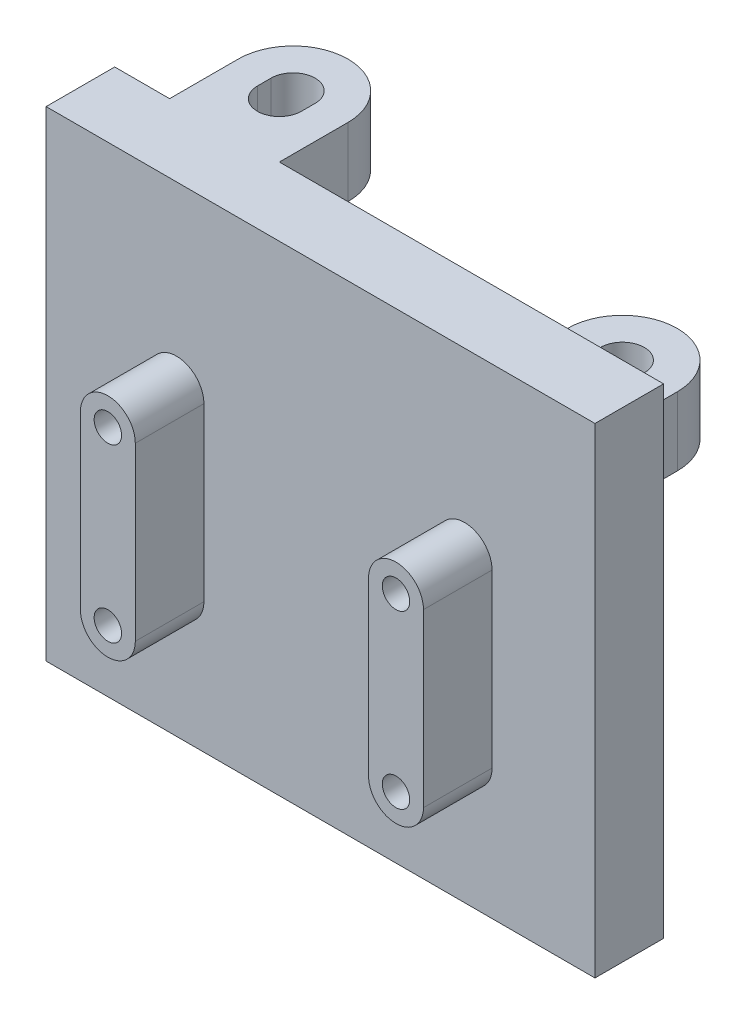
SolidWorks part; units mm, degrees
ref_plane "Front Plane" through (0, 0, 0) normal (0, 0, 1) x (1, 0, 0)
ref_plane "Top Plane" through (0, 0, 0) normal (0, 1, 0) x (1, 0, 0)
ref_plane "Right Plane" through (0, 0, 0) normal (1, 0, 0) x (0, 0, -1)
sketch "Sketch1" plane through (0, 0, 0) normal (0, 1, 0) x (1, 0, 0)
  line L0 (0, 6.621) -> (0, -6.4722) construction
  line L1 (-30, 0) -> (30, 0)
  line L2 (30, 0) -> (30, -5)
  line L3 (30, -5) -> (-30, -5)
  line L4 (-30, -5) -> (-30, 0)
  line L5 (8, 5) -> (8, 0)
  line L6 (16, 5) -> (16, 0)
  line L7 (12, 5) -> (12, 4) construction
  line L8 (13.6, 5) -> (13.6, 4)
  line L9 (10.4, 5) -> (10.4, 4)
  line L10 (-12, 5) -> (-12, 4) construction
  line L11 (-13.6, 5) -> (-13.6, 4)
  line L12 (-10.4, 5) -> (-10.4, 4)
  line L13 (-16, 5) -> (-16, 0)
  line L14 (-8, 5) -> (-8, 0)
  arc A0 (8, 5) -> (16, 5) centre (12, 5) cw
  arc A1 (13.6, 5) -> (10.4, 5) centre (12, 5) ccw
  arc A2 (10.4, 4) -> (13.6, 4) centre (12, 4) ccw
  arc A3 (-13.6, 5) -> (-10.4, 5) centre (-12, 5) cw
  arc A4 (-10.4, 4) -> (-13.6, 4) centre (-12, 4) cw
  arc A5 (-8, 5) -> (-16, 5) centre (-12, 5) ccw
  point P11 (12, 4.5)
  point P20 (-12, 4.5)
  dimension "D3" = 4
  dimension "D5" = 1.6
  dimension "D1" = 1
  dimension "D2" = 60
  dimension "D4" = 5
  dimension "D6" = 12
  dimension "D7" = 5
extrude "Boss-Extrude1" add sketch "Sketch1" along normal blind 5 contours L4 L3 L2 L1 | L14 A5 L13 L1 L12 A4 L11 A3 region at (0, 0, 2.5) region at (-15.8796, 0, -2.5)
extrude "Boss-Extrude2" add sketch "Sketch1<3>" against normal blind 5 contours A0 L5 L1 L6 A2 L9 A1 L8 | L4 L3 L2 L1 region at (0, 0, 2.5) region at (8.1204, 0, -2.5)
sketch "Sketch1<3>" plane through (0, 0, 0) normal (0, 1, 0) x (1, 0, 0) same geometry as "Sketch1"
extrude "Boss-Extrude3" add sketch "Sketch1<4>" against normal blind 30 contours L4 L3 L2 L1 region at (0, 0, 2.5)
sketch "Sketch1<4>" plane through (0, 0, 0) normal (0, 1, 0) x (1, 0, 0) same geometry as "Sketch1"
sketch "Sketch2" plane through (0, 0, 5) normal (0, 0, 1) x (1, 0, 0)
  line L0 (0, 16.7114) -> (0, -48.6728) construction
  line L1 (-30, 5) -> (-30, -30) construction
  line L2 (30, 5) -> (30, -30) construction
  line L3 (30, -30) -> (-30, -30) construction
  line L8 (-10.5, -8) -> (-10.5, -20.5) construction
  line L9 (-8.5, -8) -> (-8.5, -20.5)
  line L10 (-12.5, -8) -> (-12.5, -20.5)
  line L11 (10.5, -8) -> (10.5, -20.5) construction
  line L12 (8.5, -8) -> (8.5, -20.5)
  line L13 (12.5, -8) -> (12.5, -20.5)
  line L15 (-30, 5) -> (-20, 5)
  line L16 (-30, 5) -> (-30, -30)
  line L17 (-30, -30) -> (-20, -30)
  line L18 (-20, 5) -> (-20, -30)
  line L19 (30, 5) -> (20, 5)
  line L20 (30, 5) -> (30, -30)
  line L21 (30, -30) -> (20, -30)
  line L22 (20, 5) -> (20, -30)
  circle A0 centre (-10.5, -8) radius 1
  circle A1 centre (-10.5, -20.5) radius 1
  arc A2 (-8.5, -8) -> (-12.5, -8) centre (-10.5, -8) ccw
  arc A3 (-12.5, -20.5) -> (-8.5, -20.5) centre (-10.5, -20.5) ccw
  circle A4 centre (10.5, -20.5) radius 1
  circle A5 centre (10.5, -8) radius 1
  arc A6 (8.5, -8) -> (12.5, -8) centre (10.5, -8) cw
  arc A7 (12.5, -20.5) -> (8.5, -20.5) centre (10.5, -20.5) cw
  point P6 (-10.5, -14.25)
  point P22 (10.5, -14.25)
  line M1 (-30, 5) -> (-30, -30)
  line M2 (-30, -30) -> (30, -30)
  line M3 (30, -30) -> (30, 5)
  line M4 (30, 5) -> (-30, 5)
  dimension "D2" = 2
  dimension "D3" = 2
  dimension "D7" = 2
  dimension "D1" = 9.5
  dimension "D4" = 12.5
  dimension "D5" = 21
  dimension "D6" = 21
  dimension "D8" = 10
  dimension "D9" = 10
extrude "Cut-Extrude1" cut sketch "Sketch2" against normal through all contours L18 M4 M1 M2 | L22 M4 M2 M3 | A0 | A1 | A5 | A4 region at (-25, -12.5, 5) region at (25, -12.5, 5) region at (-10.5, -8, 5) region at (-10.5, -20.5, 5) region at (10.5, -20.5, 5) region at (10.5, -8, 5)
extrude "Boss-Extrude4" add sketch "Sketch2<3>" along normal blind 5 contours L10 A3 L9 A2 A0 A1 | A7 L13 A6 L12 A4 A5 region at (-10.5, -14.25, 5) region at (10.5, -14.25, 5)
sketch "Sketch2<3>" plane through (0, 0, 5) normal (0, 0, 1) x (1, 0, 0) same geometry as "Sketch2"
